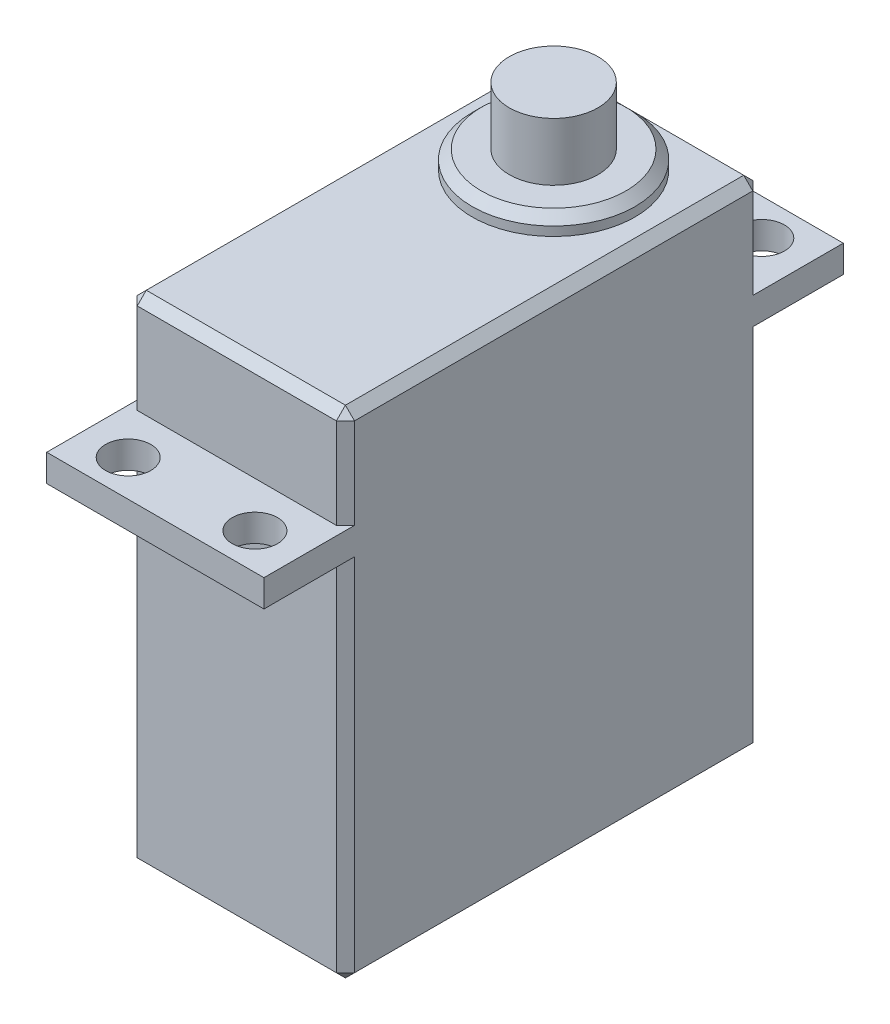
SolidWorks part; units mm, degrees
ref_plane "Front Plane" through (0, 0, 0) normal (0, 0, 1) x (1, 0, 0)
ref_plane "Top Plane" through (0, 0, 0) normal (0, 1, 0) x (1, 0, 0)
ref_plane "Right Plane" through (0, 0, 0) normal (1, 0, 0) x (0, 0, -1)
ref_axis "X Axis" through (-88.99, 0, 0) along (1, 0, 0)
ref_axis "Y Axis" through (0, 55, 0) along (0, -1, 0)
ref_axis "Z Axis" through (0, 0, -88.99) along (0, 0, 1)
sketch "Sketch1" plane through (0, 0, 0) normal (1, 0, 0) x (0, 0, -1)
  line L0 (-11.5, 27.4) -> (-11.5, 0) construction
  line L1 (0, 0) -> (-23, 0)
  line L2 (0, 0) -> (0, 27.4)
  line L3 (0, 27.4) -> (-23, 27.4)
  line L4 (-23, 0) -> (-23, 27.4)
  line L5 (-23, 21.9) -> (-27.5, 21.9)
  line L6 (-23, 21.9) -> (-23, 20.4)
  line L7 (-23, 20.4) -> (-27.5, 20.4)
  line L8 (-27.5, 21.9) -> (-27.5, 20.4)
  line L9 (0, 20.4) -> (4.5, 20.4)
  line L10 (4.5, 21.9) -> (4.5, 20.4)
  line L11 (0, 21.9) -> (4.5, 21.9)
  line L12 (0, 21.9) -> (0, 20.4)
  dimension "D1" = 23
  dimension "D2" = 27.4
  dimension "D3" = 20.4
  dimension "D4" = 32
  dimension "D5" = 1.5
extrude "Boss-Extrude1" add sketch "Sketch1" along normal mid plane 12 contours L5 L8 L7 L4 | L0 L3 L4 L1 | L3 L0 L1 L2 | L11 L2 L9 L10 region at (0, 13.7, 5.75) region at (0, 13.7, 17.25) region at (0, 21.15, -2.25) region at (0, 21.15, 25.25)
chamfer "Chamfer1" distance 0.5 angle 45 16 edges at (0, 27.4, 0) (6, 27.4, 11.5) (0, 27.4, 23) (-6, 27.4, 11.5) (0, 0, 23) (0, 0, 0) (-6, 10.2, 23) (-6, 0, 11.5) (-6, 10.2, 0) (-6, 24.65, 0) (-6, 24.65, 23) (6, 24.65, 23) (6, 10.2, 23) (6, 0, 11.5) (6, 10.2, 0) (6, 24.65, 0)
sketch "Sketch3" plane through (0, 27.4, 0) normal (0, 1, 0) x (1, 0, 0)
  line L0 (5.5, -0.5) -> (-5.5, -0.5) construction
  line L1 (0, -0.5) -> (0, -1) construction
  line L3 (-6, -11.5) -> (6, -11.5) construction
  line L4 (4.5, -5.5) -> (5, -5.5) construction
  line L5 (5, -5.5) -> (5.5, -5.5) construction
  line L6 (0, 4.5) -> (0, -27.5) construction
  line L7 (6, 4.5) -> (-6, 4.5) construction
  line L8 (6, -27.5) -> (-6, -27.5) construction
  line L9 (-6, -22.5) -> (-6, -0.5) construction
  line L10 (6, -0.5) -> (6, -22.5) construction
  line L12 (5.5, -22.5) -> (5.5, -0.5) construction
  circle A0 centre (0, -5.5) radius 4.5
  circle A1 centre (-3.5, -25.5) radius 1.25
  circle A3 centre (3.5, -25.5) radius 1.25
  circle A6 centre (0, -5.5) radius 2.45
  circle A7 centre (3.5, 2.5) radius 1.25
  circle A8 centre (-3.5, 2.5) radius 1.25
  dimension "D2" = 2.5
  dimension "D5" = 4.9
  dimension "D1" = 7
  dimension "D3" = 28
  dimension "D4" = 8
extrude "Cut-Extrude1" cut sketch "Sketch3" against normal through all contours A3 | A1 | A7 | A8
extrude "Boss-Extrude2" add sketch "Sketch3<3>" along normal blind 8 from surface contours A0 starting at face at (0, 20.4, -1.3333)
sketch "Sketch3<3>" plane through (0, 27.4, 0) normal (0, 1, 0) x (1, 0, 0) same geometry as "Sketch3"
chamfer "Chamfer2" distance 0.5 angle 45 1 edges at (0, 28.4, 10)
extrude "Boss-Extrude3" add sketch "Sketch3<4>" along normal blind 3.2 from surface contours A6 starting at face at (0, 28.4, 9.5)
sketch "Sketch3<4>" plane through (0, 27.4, 0) normal (0, 1, 0) x (1, 0, 0) same geometry as "Sketch3"
